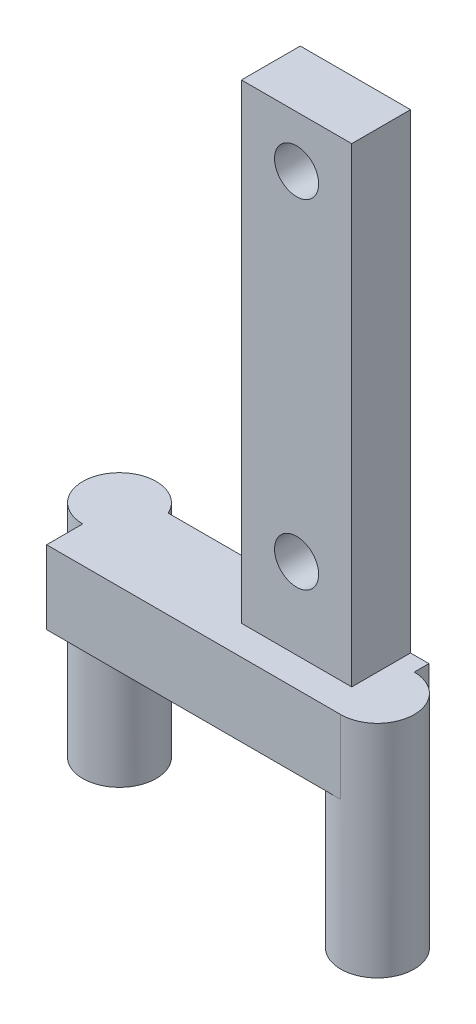
SolidWorks part; units mm, degrees
ref_plane "Front Plane" through (0, 0, 0) normal (0, 0, 1) x (1, 0, 0)
ref_plane "Top Plane" through (0, 0, 0) normal (0, 1, 0) x (1, 0, 0)
ref_plane "Right Plane" through (0, 0, 0) normal (1, 0, 0) x (0, 0, -1)
sketch "Sketch1" plane through (0, 0, 0) normal (0, 0, 1) x (1, 0, 0)
  line L0 (3.75, 26.5) -> (3.75, 3.5) construction
  line L1 (0, 0) -> (7.5, 0) construction
  line L2 (0, 0) -> (0, 30)
  line L3 (0, 30) -> (7.5, 30)
  line L4 (7.5, 0) -> (7.5, 30)
  line L5 (0, 0) -> (0, -2)
  line L6 (0, -2) -> (7.5, -2)
  line L7 (7.5, -2) -> (7.5, 0)
  circle A0 centre (3.75, 26.5) radius 1.5
  circle A1 centre (3.75, 3.5) radius 1.5
  point P9 (3.75, 15)
  point P10 (0, 15)
  point P11 (3.75, 30)
  point P14 (0, 0)
  dimension "D4" = 3
  dimension "D1" = 30
  dimension "D2" = 7.5
  dimension "D3" = 23
  dimension "D5" = 2
extrude "Boss-Extrude1" add sketch "Sketch1" along normal blind 4
sketch "Sketch2" plane through (0, -2, 0) normal (0, -1, 0) x (1, 0, 0)
  line L0 (0, 0) -> (7.5, 0) construction
  line L3 (8.75, 0) -> (-1.25, 0)
  line L4 (8.75, 0) -> (8.75, 6)
  line L5 (8.75, 6) -> (-1.25, 6)
  line L7 (-1.25, 0) -> (-1.25, 6)
  point P5 (0, 0)
  point P8 (7.5762, 0.3797)
  point P9 (0, 0)
  point P10 (0, 0)
  point P12 (0, 0)
  point P13 (0, 0)
  point P14 (0, 0)
  point P15 (0, 0)
  point P16 (0, 0)
  point P17 (3.75, 0)
  dimension "D1" = 10
  dimension "D2" = 6
extrude "Boss-Extrude2" add sketch "Sketch2" along normal blind 5
sketch "Sketch7" plane through (-1.25, 0, 0) normal (-1, 0, 0) x (0, 0, 1)
  line L1 (0, -7) -> (6, -7)
  line L2 (0, -7) -> (0, -2)
  line L3 (0, -2) -> (6, -2)
  line L4 (6, -7) -> (6, -2)
extrude "Boss-Extrude5" add sketch "Sketch7" along normal blind 10
sketch "Sketch4" plane through (0, -7, 0) normal (0, -1, 0) x (1, 0, 0)
  line L0 (-11.25, 0) -> (-11.25, 6) construction
  line L1 (-11.25, 6) -> (8.75, 6) construction
  line L3 (8.75, 3.5) -> (-11.25, 1.0443) construction
  line L4 (8.75, 3.5) -> (-11.25, 3.5) construction
  line L5 (8.75, 0) -> (8.75, 6) construction
  line L8 (-11.25, 0) -> (-11.25, 6) construction
  circle A0 centre (8.75, 3.5) radius 2.5
  circle A1 centre (-11.25, 1.0443) radius 2.5
  point P2 (0, 0)
  point P3 (0, 0)
  point P6 (0, 0)
  point P13 (0, 0)
  point P14 (0, 0)
  point P15 (0, 0)
  point P18 (0, 0)
  point P20 (0, 0)
  point P21 (0, 0)
  point P22 (0, 0)
  point P23 (0, 0)
  point P24 (0, 0)
  point P27 (0, 0)
  point P29 (0, 0)
  dimension "D1" = 5
  dimension "D2" = 2.5
  dimension "D3" = 7
extrude "Boss-Extrude3" add sketch "Sketch4" against normal up to surface (5 mm away) and the other way blind 10 up to face at (1.25, -2, 2.5)
equation "\"D2@Sketch4\"=\"D1@Sketch4\"/2"
